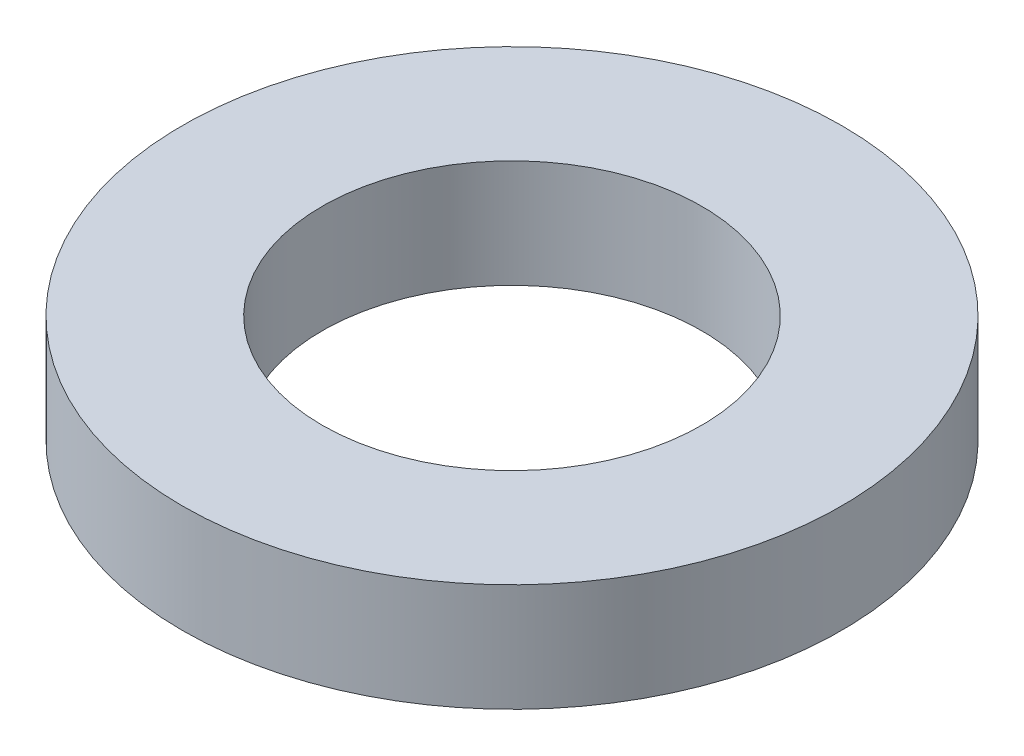
SolidWorks part; units mm, degrees
ref_plane "Front Plane" through (0, 0, 0) normal (0, 0, 1) x (1, 0, 0)
ref_plane "Top Plane" through (0, 0, 0) normal (0, 1, 0) x (1, 0, 0)
ref_plane "Right Plane" through (0, 0, 0) normal (1, 0, 0) x (0, 0, -1)
sketch "Sketch1" plane through (0, 0, 0) normal (0, 1, 0) x (1, 0, 0)
  circle A0 centre (0, 0) radius 82.5
  dimension "FLANGE_OD" = 165
extrude "Boss-Extrude1" add sketch "Sketch1" along normal blind 27
sketch "Sketch2" plane through (0, 0, 0) normal (0, 1, 0) x (1, 0, 0)
  circle A0 centre (0, 0) radius 47.5
  dimension "BORE_D" = 95
extrude "Cut-Extrude1" cut sketch "Sketch2" along normal through all
sketch "Sketch3" plane through (0, 27, 0) normal (0, 1, 0) x (1, 0, 0)
  circle A0 centre (0, 0) radius 25.4882 construction
  circle A1 centre (-25.4882, 0) radius 1.6183
  dimension "BOLT_D" = 3.2365
  dimension "BOLT_PCD" = 50.9764
extrude "Cut-Extrude2" cut sketch "Sketch3" against normal blind 16.9824 rebuild error yes
pattern_circular "CirPattern1" count 8 over 360 rebuild error yes
